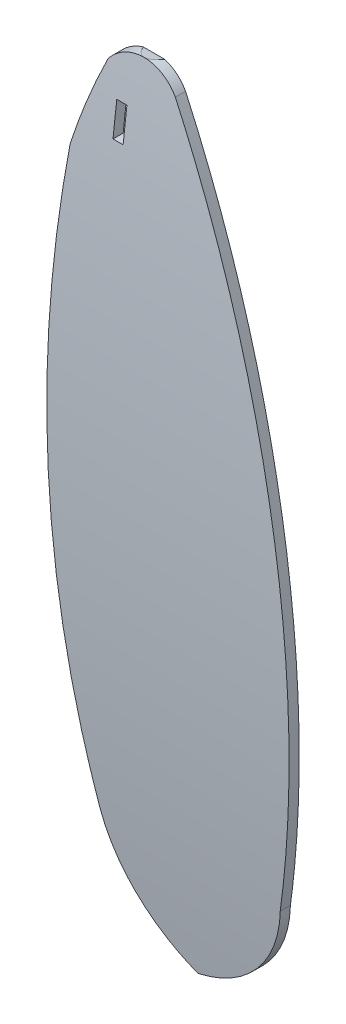
SolidWorks part; units mm, degrees
ref_plane "Front Plane" through (0, 0, 0) normal (0, 0, 1) x (1, 0, 0)
ref_plane "Top Plane" through (0, 0, 0) normal (0, 1, 0) x (1, 0, 0)
ref_plane "Right Plane" through (0, 0, 0) normal (1, 0, 0) x (0, 0, -1)
sketch "Sketch1" plane through (0, 0, 0) normal (0, 0, 1) x (1, 0, 0)
  line L1 (-1.524, 11.1196) -> (0, 11.1196)
  line L2 (-1.524, 11.1196) -> (-1.524, 15.9907)
  line L3 (-1.524, 15.9907) -> (0, 15.9907)
  line L4 (0, 11.1196) -> (0, 15.9907)
  arc A0 (6.7416, 20.1441) -> (-3.3438, 20.1441) centre (1.6989, 16.2774) ccw
  arc A1 (-3.3438, 20.1441) -> (-7.598, 7.6306) centre (73.84, -13.0757) ccw
  arc A2 (-7.598, 7.6306) -> (-3.0148, -76.3313) centre (252.5493, -20.2748) ccw
  arc A3 (-3.0148, -76.3313) -> (9.8047, -92.5066) centre (19.9579, -71.2924) ccw
  arc A4 (9.8047, -92.5066) -> (24.0847, -76.3313) centre (5.2343, -74.0808) ccw
  arc A5 (24.0847, -76.3313) -> (6.7416, 20.1441) centre (-99.173, -48.6924) ccw
extrude "Boss-Extrude1" add sketch "Sketch1" along normal blind 50.8 and the other way blind 50.8
sketch "Sketch2" plane through (0, 0, 0) normal (1, 0, 0) x (0, 0, -1)
  line L0 (0, 22.632) -> (0, 20.1441) construction
  line L1 (50.8, -92.5066) -> (-50.8, -92.5066) construction
  line L3 (1.5095, 22.4222) -> (0, 22.632)
  line L4 (1.5095, -92.2969) -> (0, -92.5066)
  arc A0 (0, 22.632) -> (0, -92.5066) centre (414.2753, -34.9373) ccw
  arc A1 (1.5095, 22.4222) -> (1.5095, -92.2969) centre (414.2753, -34.9373) ccw
  dimension "D1" = 1.524
extrude "Cut-Extrude1" cut sketch "Sketch2" against normal blind 50.8 and the other way blind 50.8 flip side to cut
